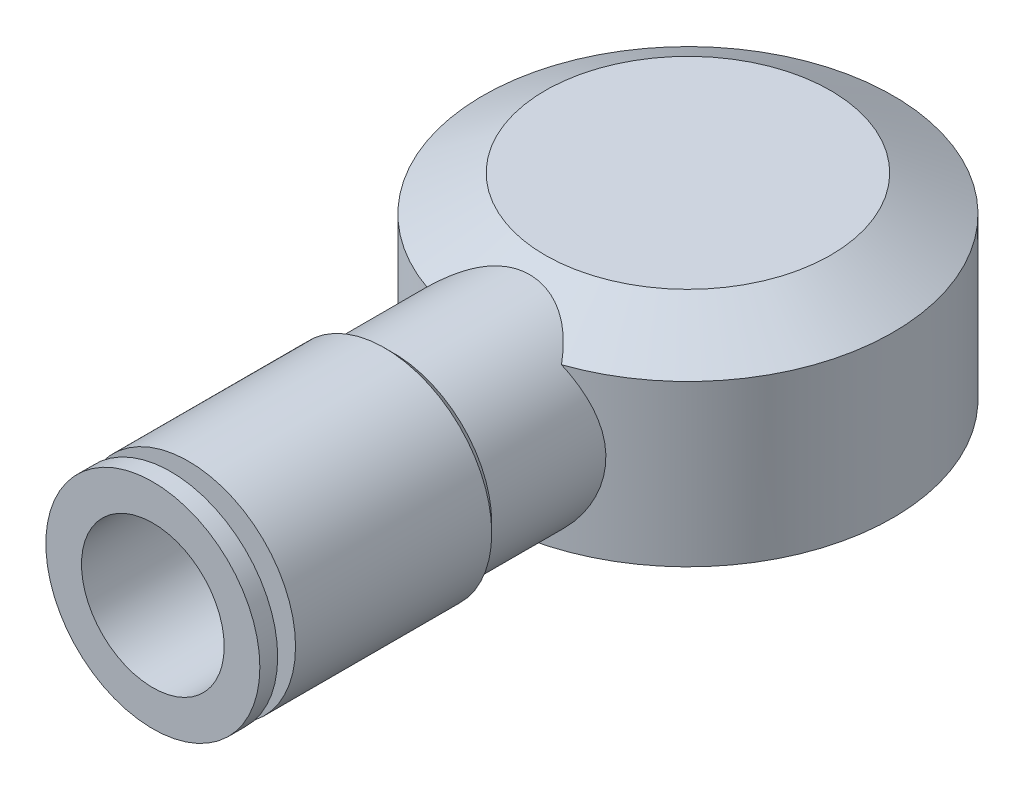
SolidWorks part; units mm, degrees
ref_plane "Front Plane" through (0, 0, 0) normal (0, 0, 1) x (1, 0, 0)
ref_plane "Top Plane" through (0, 0, 0) normal (0, 1, 0) x (1, 0, 0)
ref_plane "Right Plane" through (0, 0, 0) normal (1, 0, 0) x (0, 0, -1)
sketch "Sketch1" plane through (0, 0, 0) normal (0, 0, 1) x (1, 0, 0)
  line L0 (11.5, 3.5) -> (8, 5.5)
  line L1 (0, 5.5) -> (8, 5.5)
  line L2 (0, 5.5) -> (0, -5.5)
  line L3 (0, -5.5) -> (11.5, -5.5)
  line L4 (11.5, 3.5) -> (11.5, -5.5)
  line L5 (5.75, -5.5) -> (5.75, 5.5) construction
  line L6 (0, 0) -> (11.5, 0) construction
  dimension "D1" = 11
  dimension "D2" = 2
  dimension "D3" = 8
  dimension "D4" = 11.5
revolve "Revolve2" add sketch "Sketch1" angle 360 about L2
sketch "Sketch2" plane through (0, 0, 0) normal (0, 0, 1) x (1, 0, 0)
  line L0 (-11.5, -5.5) -> (11.5, -5.5) construction
  line L1 (-11.5, 3.5) -> (-11.5, -5.5) construction
  circle A0 centre (0, -0.5) radius 5.5
  dimension "D1" = 11
  dimension "D2" = 5
  dimension "D3" = 11.5
extrude "Boss-Extrude4" add sketch "Sketch2" along normal blind 30
sketch "Sketch3" plane through (0, 0, 30) normal (0, 0, 1) x (1, 0, 0)
  circle A0 centre (0, -0.5) radius 4.5
  circle A1 centre (0, -0.5) radius 5.5 construction
  circle A2 centre (0, -0.5) radius 5.5
  dimension "D1" = 9
extrude "Cut-Extrude1" cut sketch "Sketch3" against normal blind 1 from offset 1 offset against normal yes
sketch "Sketch5" plane through (0, -5.5, 0) normal (0, -1, 0) x (1, 0, 0)
  line L3 (2.2913, 11.2694) -> (2.2913, 0)
  line L4 (2.2913, 0) -> (-2.2913, 0)
  line L5 (-2.2913, 0) -> (-2.2913, 11.2694)
  line L6 (2.2913, 11.2694) -> (2.2913, 0)
  line L7 (2.2913, 0) -> (-2.2913, 0)
  line L8 (-2.2913, 0) -> (-2.2913, 11.2694)
  circle A0 centre (0, 0) radius 11.5
  arc A1 (-2.2913, 11.2694) -> (2.2913, 11.2694) centre (0, 0) ccw
  arc A2 (-2.2913, 11.2694) -> (2.2913, 11.2694) centre (0, 0) ccw
  dimension "D1" = 0
extrude "Cut-Extrude3" cut sketch "Sketch5" along normal blind 6 contours A0
sketch "Sketch8" plane through (0, 0, 30) normal (0, 0, 1) x (1, 0, 0)
  circle A0 centre (0, -0.5) radius 4
  dimension "D1" = 8
extrude "Cut-Extrude4" cut sketch "Sketch8" against normal blind 34
sketch "Sketch9" plane through (0, 5.5, 0) normal (0, 1, 0) x (1, 0, 0)
  circle A0 centre (0, 0) radius 7
  circle A1 centre (0, 0) radius 8
  circle A2 centre (0, 0) radius 8
  dimension "D1" = 0
  dimension "D2" = 1
extrude "Cut-Extrude6" cut sketch "Sketch9" against normal blind 34 from offset 1 contours A0 region at (0, 5.5, 0) offset against normal yes
sketch "Sketch10" plane through (0, 0, 30) normal (0, 0, 1) x (1, 0, 0)
  circle A0 centre (0, -0.5) radius 6
  circle A1 centre (0, -0.5) radius 5.5 construction
  circle A2 centre (0, -0.5) radius 5.5
  dimension "D1" = 12
extrude "Boss-Extrude5" add sketch "Sketch10" against normal up to surface (1 mm away) up to face at (4.5, -0.5, 29)
sketch "Sketch11" plane through (0, 0, 28) normal (0, 0, 1) x (1, 0, 0)
  circle A0 centre (0, -0.5) radius 6 construction
  circle A1 centre (0, -0.5) radius 5.5
  circle A2 centre (0, -0.5) radius 5.5
  circle A3 centre (0, -0.5) radius 6
  dimension "D1" = 0
extrude "Boss-Extrude6" add sketch "Sketch11" against normal blind 12
chamfer "Chamfer1" distance 1 angle 45 1 edges at (6, -0.5, 16)
other "CPoint1" parameters "Diameter"=12.7, "StubLength"=10
ref_axis "Axis1" through (0, -0.5, 40) along (0, 0, -1)
